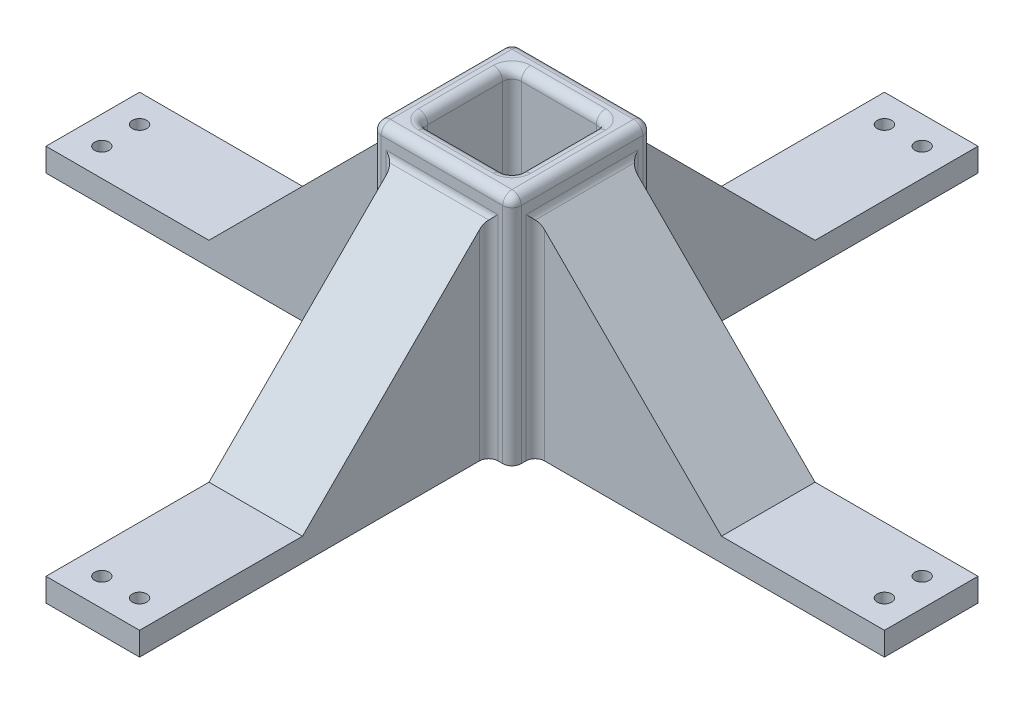
SolidWorks part; units mm, degrees
ref_plane "Front Plane" through (0, 0, 0) normal (0, 0, 1) x (1, 0, 0)
ref_plane "Top Plane" through (0, 0, 0) normal (0, 1, 0) x (1, 0, 0)
ref_plane "Right Plane" through (0, 0, 0) normal (1, 0, 0) x (0, 0, -1)
sketch "Sketch1" plane through (0, 0, 0) normal (0, 1, 0) x (1, 0, 0)
  line L0 (0, 0) -> (-20.1, 0) construction
  line L1 (0, 0) -> (80, 0)
  line L2 (0, 0) -> (0, 20.1)
  line L3 (0, 20.1) -> (80, 20.1)
  line L4 (80, 0) -> (80, 20.1)
  line L8 (-20.1, 20.1) -> (-20.1, 0)
  line L9 (-20.1, 20.1) -> (0, 0) construction
  line L10 (-20.1, 20.1) -> (0, 20.1)
  line L11 (-20.1, 20.1) -> (-20.1, 0)
  line L12 (-20.1, 0) -> (0, 0)
  line L13 (0, 20.1) -> (0, 0)
  line L14 (-20.1, 0) -> (0, 20.1) construction
  line L15 (-20.1, 0) -> (-20.1, -80)
  line L16 (0, 0) -> (0, -80)
  line L17 (-20.1, -80) -> (0, -80)
  line L18 (-20.1, 0) -> (0, 0)
  line L19 (-20.1, 20.1) -> (-100.1, 20.1)
  line L20 (-20.1, 0) -> (-100.1, 0)
  line L21 (-100.1, 20.1) -> (-100.1, 0)
  line L22 (-20.1, 20.1) -> (-20.1, 0)
  line L23 (0, 20.1) -> (0, 100.1)
  line L24 (-20.1, 20.1) -> (-20.1, 100.1)
  line L25 (0, 100.1) -> (-20.1, 100.1)
  line L26 (0, 20.1) -> (-20.1, 20.1)
  line L28 (-25.1, 25.1) -> (5, 25.1)
  line L29 (-25.1, 25.1) -> (-25.1, -5)
  line L30 (-25.1, -5) -> (5, -5)
  line L31 (5, 25.1) -> (5, -5)
  circle A5 centre (74, 14.1) radius 1.55
  circle A7 centre (74, 6) radius 1.55
  circle A9 centre (-6, -74) radius 1.55
  circle A11 centre (-14.1, -74) radius 1.55
  circle A13 centre (-94.1, 6) radius 1.55
  circle A15 centre (-94.1, 14.1) radius 1.55
  circle A17 centre (-14.1, 94.1) radius 1.55
  circle A19 centre (-6, 94.1) radius 1.55
  point P11 (-10.05, 10.05)
  point P56 (-10.05, 10.05)
  dimension "D4" = 4
  dimension "D7" = 5
  dimension "D8" = 5
  dimension "D9" = 5
  dimension "D11" = 3.1
  dimension "D13" = 3.1
  dimension "D3" = 20.1
  dimension "D5" = 80
  dimension "D6" = 5
  dimension "D24" = 6
  dimension "D25" = 6
  dimension "D26" = 6
  dimension "D27" = 6
extrude "Boss-Extrude1" add sketch "Sketch1" along normal blind 5 contours L1 L4 L3 L2 A7 A5 | L23 L25 L24 L10 A19 A17 | L19 L21 L20 L8 A15 A13 | L15 L17 L16 L12 A11 A9 region at (42.1814, 0, -10.05) region at (-10.05, 0, 42.1814) region at (-10.05, 0, -62.2814) region at (-62.2814, 0, -10.05)
extrude "Boss-Extrude2" add sketch "Sketch1<8>" along normal blind 50 contours L28 L29 L19 L24 | L28 L24 L10 L23 | L19 L29 L20 L8 | L31 L28 L23 L3 | L31 L3 L2 L1 | L31 L1 L16 L30 | L15 L30 L16 L12 | L29 L30 L15 L20 region at (2.5, 0, -10.05) region at (-10.05, 0, 2.5) region at (2.5, 0, 2.5) region at (2.5, 0, -22.6) region at (-10.05, 0, -22.6) region at (-22.6, 0, -10.05) region at (-22.6, 0, 2.5) region at (-22.6, 0, -22.6)
sketch "Sketch1<8>" plane through (0, 0, 0) normal (0, 1, 0) x (1, 0, 0) same geometry as "Sketch1"
chamfer "Chamfer1" distance 40 angle 45 4 edges at (-10.05, 5, -25.1) (5, 5, -10.05) (-10.05, 5, 5) (-25.1, 5, -10.05)
fillet "Fillet1" radius 2 28 edges at (-10.05, 50, -20.1) (-20.1, 50, -10.05) (-10.05, 50, 0) (0, 50, -10.05) (-25.1, 50, -10.05) (-10.05, 50, -25.1) (5, 50, -10.05) (-10.05, 50, 5) (-10.05, 45, 5) (5, 45, -10.05) (-10.05, 45, -25.1) (-25.1, 45, -10.05) (-25.1, 22.5, -20.1) (-25.1, 25, -25.1) (-20.1, 22.5, -25.1) (0, 22.5, -25.1) (5, 25, -25.1) (5, 22.5, -20.1) (0, 25, -20.1) (0, 22.5, 5) (5, 22.5, 0) (5, 25, 5) (-20.1, 22.5, 5) (-25.1, 22.5, 0) (-25.1, 25, 5) (0, 25, 0) (-20.1, 25, 0) (-20.1, 25, -20.1)
